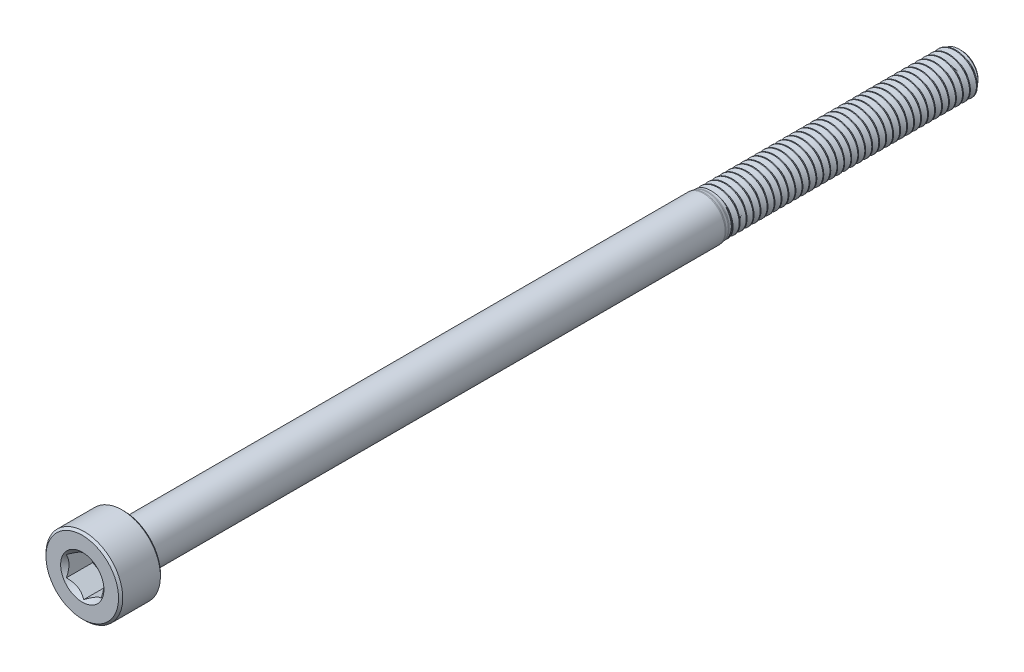
SolidWorks part; units mm, degrees
ref_plane "Front Plane" through (0, 0, 0) normal (0, 0, 1) x (1, 0, 0)
ref_plane "Top Plane" through (0, 0, 0) normal (0, 1, 0) x (1, 0, 0)
ref_plane "Right Plane" through (0, 0, 0) normal (1, 0, 0) x (0, 0, -1)
sketch "Sketch1" plane through (0, 0, 0) normal (1, 0, 0) x (0, 0, -1)
  line L0 (-31.5, 0) -> (31.5, 0) construction
  line L1 (31.5, 0) -> (31.5, 1.1752) construction
  line L2 (31.5, 1.1752) -> (31.1752, 1.5) construction
  line L3 (31.1752, 1.5) -> (31.125, 1.5) construction
  line L4 (31.125, 1.5) -> (-28.5, 1.5) construction
  line L5 (-28.5, 1.5) -> (-28.5, 2.75) construction
  line L6 (-28.5, 2.75) -> (-31.5, 2.75) construction
  line L7 (-31.5, 2.75) -> (-31.5, 0) construction
  line L8 (31.5, 1.1752) -> (31.5, 1.5) construction
  line L9 (31.4688, 1.5541) -> (31.7188, 1.1211) construction
  line L10 (31.7188, 1.1211) -> (31.9688, 1.5541) construction
  line L11 (31.9688, 1.5541) -> (31.4688, 1.5541) construction
  line L12 (31.7188, 1.5541) -> (31.7187, 1.5) construction
  line L13 (31.7188, 1.1211) -> (31.7188, 1.1752) construction
  line L14 (31.6875, 1.1752) -> (31.75, 1.1752) construction
  line L15 (31.5, 1.5) -> (31.9375, 1.5) construction
  line L16 (31.4844, 1.5271) -> (31.9531, 1.5271) construction
  line L17 (31.5, 0) -> (31.5, -1.5) construction
  line L18 (-28.65, 2.75) -> (-28.5, 2.6) construction
  line L19 (-31.35, 2.75) -> (-31.5, 2.6) construction
  line L20 (-28.5, 1.5) -> (-28.5, 0) construction
  line L21 (-28.5, 0.75) -> (-8.5, 0.75) construction
  line L22 (-8.5, 0.75) -> (11.5, 0.75) construction
  line L23 (11.5, 0.75) -> (31.5, 0.75) construction
  line L24 (-8.5, 0.75) -> (-8.5, 1.5) construction
  line L25 (-8.5, 1.5) -> (-8.5, 2.75) construction
  line L26 (11.5, 0.75) -> (11.5, 2.75) construction
  point P0 (-31.5, 1.25)
  point P3 (30.25, 1.5)
  point P4 (0, 0)
  point P18 (11.5, 1.5)
  point P22 (31.7188, 1.1752)
  point P24 (31.125, 1.5)
  point P25 (31.7187, 1.5)
  point P28 (31.7188, 1.5271)
  point P29 (30.25, -1.5)
  point P30 (-8.5, 1.5)
  point P31 (-30, 2.75)
  point P37 (-29.025, 2.75)
  point P38 (-31.275, 2.75)
  point P45 (-8.5, 0.75)
  point P46 (11.5, 0.75)
  point P49 (13.5, 1.5)
  dimension "D1" = 45
  dimension "D2" = 0.0625
  dimension "D7" = 0.15
  dimension "D8" = 0.15
  dimension "D9" = 0.15
  dimension "D10" = 0.075
  dimension "D11" = 0.375
  dimension "Drive Size" = 2.5
  dimension "Head Diameter" = 5.5
  dimension "Head Height" = 3
  dimension "Thread Pitch" = 0.5
  dimension "Thread Dia" = 3
  dimension "Length" = 60
  dimension "D12" = 0.375
  dimension "D4" = 1.25
  dimension "Minimum Thread Length" = 18
  dimension "D3" = 42
sketch "Sketch2" plane through (0, 0, 0) normal (1, 0, 0) x (0, 0, -1)
  line L0 (-31.5, 0) -> (-31.5, 2.6)
  line L1 (-31.35, 2.75) -> (-28.65, 2.75)
  line L2 (-28.5, 2.6) -> (-28.5, 1.7041)
  line L4 (31.1752, 1.5) -> (31.5, 1.1752)
  line L5 (31.5, 1.1752) -> (31.5, 0)
  line L6 (-28.5, 2.75) -> (-31.5, 2.75) construction
  line L7 (31.5, 0) -> (-31.5, 0)
  line L8 (-31.35, 2.75) -> (-31.5, 2.6) construction
  line L10 (-31.35, 2.75) -> (-31.5, 2.6)
  line L14 (-28.65, 2.75) -> (-28.5, 2.6) construction
  line L16 (-28.65, 2.75) -> (-28.5, 2.6)
  line L17 (-28.5, 1.5) -> (-28.5, 2.75) construction
  line L18 (-28.35, 1.5541) -> (13.0035, 1.5541)
  line L19 (13.3494, 1.5) -> (31.1752, 1.5)
  line L20 (31.125, 1.5) -> (-28.5, 1.5) construction
  line L21 (13.0766, 1.5469) -> (13.2763, 1.5072)
  line L22 (31.9688, 1.5541) -> (31.4688, 1.5541) construction
  arc A1 (-28.5, 1.7041) -> (-28.35, 1.5541) centre (-28.35, 1.7041) ccw
  arc A2 (13.0035, 1.5541) -> (13.0766, 1.5469) centre (13.0035, 1.1791) cw
  arc A3 (13.2763, 1.5072) -> (13.3494, 1.5) centre (13.3494, 1.875) ccw
  point P39 (13.3125, 1.5)
  dimension "D3" = 0.15
  dimension "D6" = 0.375
  dimension "D4" = 11.25
  dimension "D5" = 0.1875
revolve "Revolve1" add sketch "Sketch2" angle 360 about L7
sketch "Sketch3" plane through (0, 0, 31.5) normal (0, 0, 1) x (1, 0, 0)
  line L1 (1.25, -0.7217) -> (1.25, 0.7217)
  line L2 (1.25, 0.7217) -> (0, 1.4434)
  line L3 (0, 1.4434) -> (-1.25, 0.7217)
  line L4 (-1.25, 0.7217) -> (-1.25, -0.7217)
  line L5 (-1.25, -0.7217) -> (0, -1.4434)
  line L6 (0, -1.4434) -> (1.25, -0.7217)
  circle A0 centre (0, 0) radius 1.25 construction
  circle A1 centre (0, 0) radius 2.75 construction
  circle A2 centre (0, 0) radius 2.75 construction
  circle A3 centre (0, 0) radius 1.4434 construction
  dimension "D1" = 2.8868
extrude "Cut-Extrude1" cut sketch "Sketch3" against normal offset from surface (2 mm away) 1 up to face at (0, 2.6, 28.5)
sketch "Sketch4" plane through (0, 0, 31.5) normal (0, 0, 1) x (1, 0, 0)
  circle A0 centre (0, 0) radius 1.5516
  dimension "D1" = 3.1033
extrude "Cut-Extrude2" cut sketch "Sketch4" against normal up to vertex (1.5 mm away) draft 45 up to point (0, 2.75, 30)
sketch "Sketch11" plane through (0, 0, 0) normal (1, 0, 0) x (0, 0, -1)
  line L0 (-31.5, 0) -> (31.5, 0) construction
  line L1 (-31.5, 0) -> (31.5, 0) construction
  line L2 (-24.825, 0) -> (-24.825, 1.5) construction
  line L3 (31.125, 1.5) -> (-28.5, 1.5) construction
  line L4 (9.3285, 0) -> (9.3285, 1.5) construction
  point P2 (-24.825, 0)
  point P3 (9.3285, 0)
  dimension "D1" = 3.675
  dimension "D2" = 3.675
sketch "Sketch6" plane through (0, 0, -31.5) normal (0, 0, -1) x (-1, 0, 0)
  circle A0 centre (0, 0) radius 1.5
curve "Helix/Spiral1" pitch 0.5 height 18.5 turns 37
sketch "Sketch10" plane through (0, 0, 0) normal (1, 0, 0) x (0, 0, -1)
  line L0 (13.5, -1.5) -> (13.5, 1.5)
  line L2 (-31.5, 0) -> (31.5, 0) construction
  point P3 (13.5, 0)
split "Split1" trim tools "Sketch10" bodies to split 106 resulting bodies 114 115
sketch "Sketch7" plane through (0, 0, 0) normal (1, 0, 0) x (0, 0, -1)
  line L0 (31.4844, 1.5271) -> (31.9531, 1.5271)
  line L1 (31.9531, 1.5271) -> (31.75, 1.1752)
  line L2 (31.75, 1.1752) -> (31.6875, 1.1752)
  line L3 (31.6875, 1.1752) -> (31.4844, 1.5271)
sweep "Cut-Sweep1" cut profiles "Sketch7" path "Helix/Spiral1" align with end faces yes
sketch "Sketch8" plane through (0, 0, 0) normal (1, 0, 0) x (0, 0, -1)
  line L0 (-28.5, 0) -> (-28.5, 1.5)
  line L2 (-28.5, 1.5) -> (13.5, 1.5)
  line L4 (13.5, 1.5) -> (14.366, 0)
  line L5 (14.366, 0) -> (-28.5, 0)
  line L6 (31.125, 1.5) -> (-28.5, 1.5) construction
  line L7 (-31.5, 0) -> (31.5, 0) construction
  dimension "D1" = 60
  dimension "D2" = 18
revolve "Revolve2" add sketch "Sketch8" angle 360 about L5
equation "\"D2@Sketch1\" = \"Thread Pitch@Sketch1\" / 8"
equation "\"D4@Helix/Spiral1\" = \"Thread Pitch@Sketch1\""
equation "\"D7@Sketch1\" = \"Head Height@Sketch1\" * .05"
equation "\"D8@Sketch1\"=\"D7@Sketch1\""
equation "\"D9@Sketch1\"=\"D7@Sketch1\""
equation "\"D10@Sketch1\"=\"D7@Sketch1\"/2"
equation "\"D11@Sketch1\"=\"D10@Sketch1\"*5"
equation "\"D4@Sketch1\"=\"Thread Pitch@Sketch1\"*2.5"
equation "\"D12@Sketch1\"=\"Thread Pitch@Sketch1\"*.75"
equation "\"D3@Helix/Spiral1\"=\"Minimum Thread Length@Sketch1\"+\"Thread Pitch@Sketch1\""
equation "\"D2@Sketch8\"=\"Minimum Thread Length@Sketch1\""
equation "\"D3@Sketch2\"=\"Thread Dia@Sketch1\"*0.05"
equation "\"D5@Sketch2\"=\"D12@Sketch1\"*0.5"
equation "\"D6@Sketch2\"=\"Thread Dia@Sketch1\"*0.125"
equation "\"D1@Sketch11\"=\"D3@Sketch1\"*0.0875"
equation "\"D2@Sketch11\"=\"D1@Sketch11\""
equation "\"D1@Sketch4\"=\"D1@Sketch3\"*1.075"
